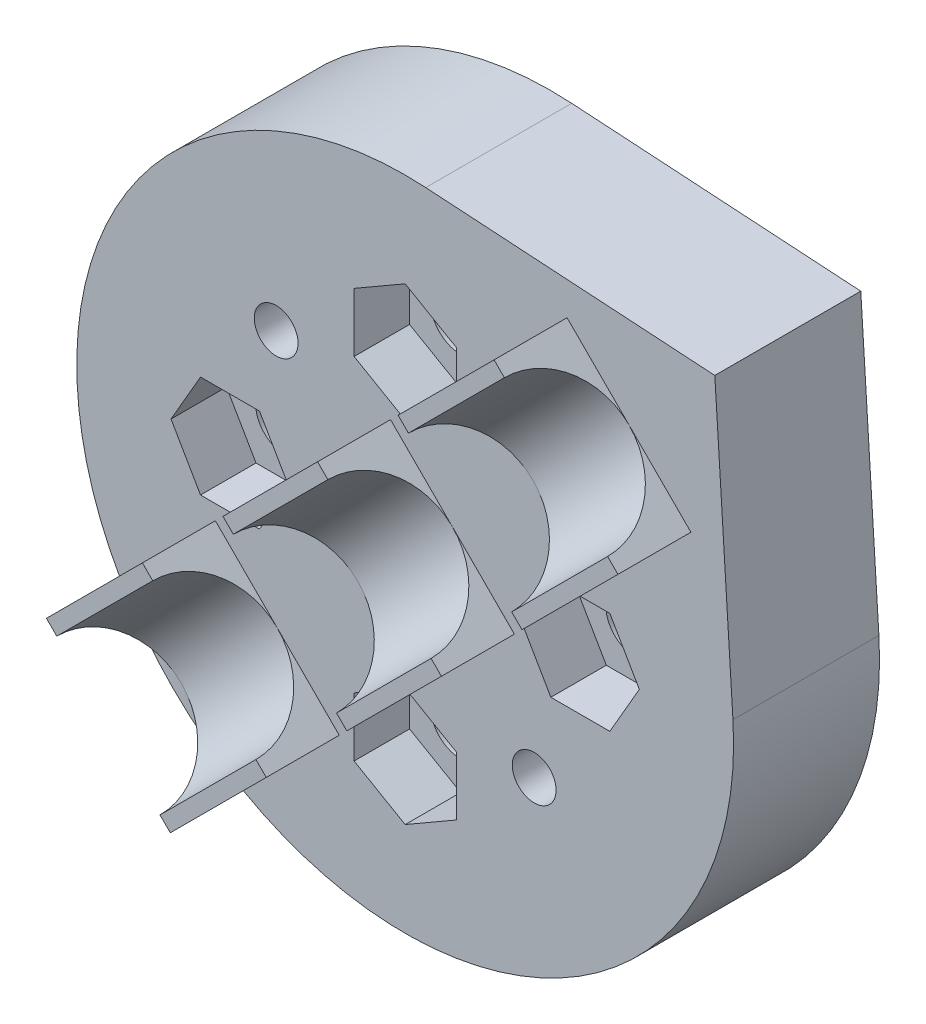
SolidWorks part; units mm, degrees
ref_plane "Front Plane" through (0, 0, 0) normal (1, 0, 0) x (0, 1, 0)
ref_plane "Top Plane" through (0, 0, 0) normal (0, 0, 1) x (0, 1, 0)
ref_plane "Right Plane" through (0, 0, 0) normal (0, 1, 0) x (-1, 0, 0)
sketch "Sketch1" plane through (0, 0, 0) normal (0, 0, 1) x (0, 1, 0)
  line L0 (21.2132, -21.2132) -> (1.409, -22.4558)
  line L1 (21.2132, -21.2132) -> (22.4558, -1.409)
  line L2 (21.2132, -21.2132) -> (0, 0) construction
  line L3 (7.9585, 0) -> (9.9793, -3.5)
  line L4 (0, 7.9585) -> (3.5, 9.9793)
  line L5 (3.5, 9.9793) -> (3.5, 14.0207)
  line L6 (3.5, 14.0207) -> (0, 16.0415)
  line L7 (0, 16.0415) -> (-3.5, 14.0207)
  line L8 (-3.5, 14.0207) -> (-3.5, 9.9793)
  line L9 (-3.5, 9.9793) -> (0, 7.9585)
  line L10 (9.9793, -3.5) -> (14.0207, -3.5)
  line L11 (14.0207, -3.5) -> (16.0415, 0)
  line L12 (16.0415, 0) -> (14.0207, 3.5)
  line L13 (14.0207, 3.5) -> (9.9793, 3.5)
  line L14 (9.9793, 3.5) -> (7.9585, 0)
  line L15 (0, -7.9585) -> (-3.5, -9.9793)
  line L16 (-3.5, -9.9793) -> (-3.5, -14.0207)
  line L17 (-3.5, -14.0207) -> (0, -16.0415)
  line L18 (0, -16.0415) -> (3.5, -14.0207)
  line L19 (3.5, -14.0207) -> (3.5, -9.9793)
  line L20 (3.5, -9.9793) -> (0, -7.9585)
  line L21 (-7.9585, 0) -> (-9.9793, 3.5)
  line L22 (-9.9793, 3.5) -> (-14.0207, 3.5)
  line L23 (-14.0207, 3.5) -> (-16.0415, 0)
  line L24 (-16.0415, 0) -> (-14.0207, -3.5)
  line L25 (-14.0207, -3.5) -> (-9.9793, -3.5)
  line L26 (-9.9793, -3.5) -> (-7.9585, 0)
  line L27 (0, 0) -> (0, 12) construction
  circle A0 centre (0, 0) radius 16.25
  arc A1 (22.4558, -1.409) -> (1.409, -22.4558) centre (0, 0) ccw
  circle A2 centre (0, 0) radius 12 construction
  circle A3 centre (0, 12) radius 2.05
  circle A4 centre (0, 12) radius 3.5 construction
  circle A5 centre (12, 0) radius 2.05
  circle A6 centre (0, -12) radius 2.05
  circle A7 centre (-12, 0) radius 2.05
  point P3 (23.7538, -18.3237)
  dimension "D1" = 32.5
  dimension "D2" = 45
  dimension "D4" = 24
  dimension "D5" = 4.1
  dimension "D3" = 30
  dimension "D6" = 7
  dimension "D8" = 135
  dimension "D7" = 4
extrude "Boss-Extrude1" add sketch "Sketch1" along normal blind 10 contours L1 A1 L0 A0 region at (21.1994, 11.2713, 0)
extrude "Boss-Extrude2" add sketch "Sketch1<3>" along normal up to surface (10 mm away) from offset 3.1 contours A0 L9 L8 L7 L6 L5 L4 L14 L13 L12 L11 L10 L3 L20 L19 L18 L17 L16 L15 L26 L25 L24 L23 L22 L21 region at (0, 0, 0) up to face at (16.25, 0, 10)
sketch "Sketch1<3>" plane through (0, 0, 0) normal (0, 0, 1) x (0, 1, 0) same geometry as "Sketch1"
extrude "Boss-Extrude3" add sketch "Sketch1<4>" along normal blind 3.1 from surface contours L19 L20 L15 L16 L17 L18 A6 | L13 L14 L3 L10 L11 L12 A5 | L8 L9 L4 L5 L6 L7 A3 | L25 L26 L21 L22 L23 L24 A7 region at (-1.6965, 9.0615, 0) region at (-9.0615, -1.6965, 0) region at (9.0615, 1.6965, 0) region at (1.6965, -9.0615, 0) starting at face at (-12, 0, 3.1)
sketch "Sketch1<4>" plane through (0, 0, 0) normal (0, 0, 1) x (0, 1, 0) same geometry as "Sketch1"
sketch "Sketch2" plane through (0, 0, 10) normal (0, 0, 1) x (1, 0, 0)
  line L0 (11.0911, 19.5764) -> (-19.5764, -11.0911)
  line L1 (11.0911, 19.5764) -> (19.5764, 11.0911)
  line L2 (-19.5764, -11.0911) -> (-11.0911, -19.5764)
  line L3 (19.5764, 11.0911) -> (-11.0911, -19.5764)
  line L4 (11.0911, 19.5764) -> (-11.0911, -19.5764) construction
  line L5 (-19.5764, -11.0911) -> (19.5764, 11.0911) construction
  line L6 (0, 0) -> (12, 0) construction
  line L7 (-18.8693, -11.7983) -> (11.7983, 18.8693)
  line L8 (-11.7983, -18.8693) -> (18.8693, 11.7983)
  line L9 (-8.8388, 8.8388) -> (8.8388, -8.8388) construction
  line L10 (-14.0207, -3.5) -> (-3.5, -14.0207)
  line L11 (-9.9793, 3.5) -> (3.5, -9.9793)
  line L12 (3.5, 14.0207) -> (14.0207, 3.5)
  line L13 (9.9793, -3.5) -> (-3.5, 9.9793)
  arc A0 (1.409, 22.4558) -> (22.4558, 1.409) centre (0, 0) ccw construction
  circle A1 centre (8.8388, -8.8388) radius 1.5
  circle A2 centre (-8.8388, 8.8388) radius 1.5
  point P1 (0, 0)
  point P18 (0, 0)
  dimension "D7" = 3
  dimension "D8" = 3
  dimension "D1" = 45
  dimension "D2" = 12
  dimension "D3" = 10
  dimension "D4" = 1
  dimension "D5" = 45
  dimension "D6" = 25
extrude "Cut-Extrude1" cut sketch "Sketch2" against normal through all both and the other way through all contours A2 | A1
extrude "Boss-Extrude4" add sketch "Sketch2<3>" along normal blind 5 contours L10 L7 L2 L8 | L10 L0 L2 L7 | L10 L8 L2 L3 | L8 L13 L7 L11 | L7 L13 L0 L11 | L3 L13 L8 L11 | L8 L12 L3 L1 | L7 L12 L8 L1 | L0 L12 L7 L1 region at (8.158, 15.9362, 10) region at (12.0471, 12.0471, 10) region at (-3.8891, 3.8891, 10) region at (15.9362, 8.158, 10) region at (0, 0, 10) region at (-15.9362, -8.158, 10) region at (3.8891, -3.8891, 10) region at (-12.0471, -12.0471, 10) region at (-8.158, -15.9362, 10)
sketch "Sketch2<3>" plane through (0, 0, 10) normal (0, 0, 1) x (1, 0, 0) same geometry as "Sketch2"
sketch "Sketch3" plane through (-15.3338, -15.3338, 0) normal (-0.7071, -0.7071, 0) x (0.7071, -0.7071, 0)
  line L0 (-6, 15) -> (6, 15) construction
  circle A0 centre (0, 15) radius 5
  dimension "D1" = 10
extrude "Cut-Extrude2" cut sketch "Sketch3" against normal through all both and the other way through all contours A0
